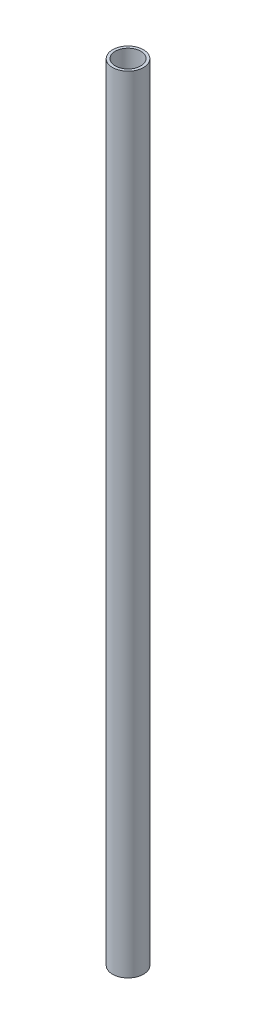
SolidWorks part; units mm, degrees
material "Carbon Fiber (2)"
ref_plane "Front Plane" through (0, 0, 0) normal (0, 0, 1) x (1, 0, 0)
ref_plane "Top Plane" through (0, 0, 0) normal (0, 1, 0) x (1, 0, 0)
ref_plane "Right Plane" through (0, 0, 0) normal (1, 0, 0) x (0, 0, -1)
sketch "Sketch1" plane through (0, 0, 0) normal (0, 1, 0) x (1, 0, 0)
  circle A0 centre (0, 0) radius 4.953
  circle A1 centre (0, 0) radius 5.9944
  dimension "D1" = 9.906
  dimension "D2" = 11.9888
extrude "Boss-Extrude1" add sketch "Sketch1" along normal blind 304.8
